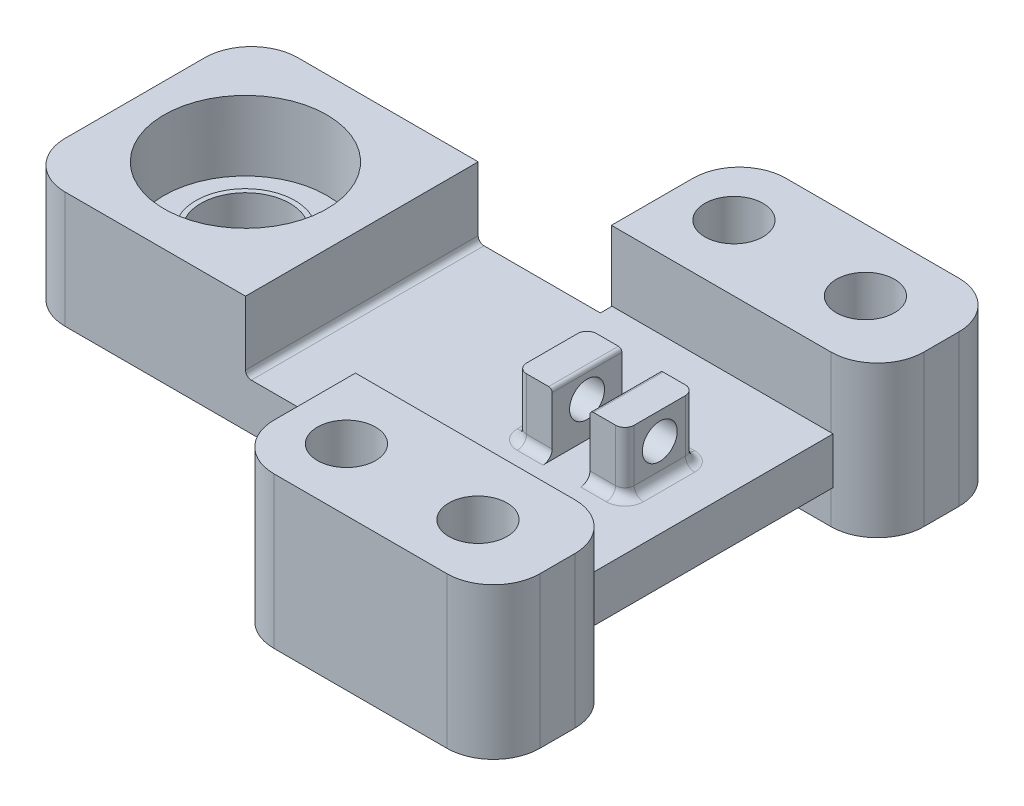
SolidWorks part; units mm, degrees
ref_plane "Front Plane" through (0, 0, 0) normal (0, 0, 1) x (1, 0, 0)
ref_plane "Top Plane" through (0, 0, 0) normal (0, 1, 0) x (1, 0, 0)
ref_plane "Right Plane" through (0, 0, 0) normal (1, 0, 0) x (0, 0, -1)
sketch "Sketch2" plane through (0, 0, 0) normal (0, 1, 0) x (1, 0, 0)
  line L1 (-14.4231, 13.5577) -> (34.5769, 13.5577)
  line L2 (-14.4231, 13.5577) -> (-14.4231, -6.4423)
  line L3 (-14.4231, -6.4423) -> (34.5769, -6.4423)
  line L4 (34.5769, 13.5577) -> (34.5769, -6.4423)
  dimension "D1" = 49
  dimension "D2" = 20
extrude "Boss-Extrude1" add sketch "Sketch2" along normal blind 10
sketch "Sketch3" plane through (0, 0, 0) normal (0, -1, 0) x (1, 0, 0)
  line L0 (34.5769, 6.4423) -> (34.5769, -13.5577) construction
  line L1 (27.5769, -5.0677) -> (-2.4231, -5.0677)
  line L2 (27.5769, -5.0677) -> (27.5769, -2.0477)
  line L3 (27.5769, -2.0477) -> (-2.4231, -2.0477)
  line L4 (-2.4231, -5.0677) -> (-2.4231, -2.0477)
  line L5 (-14.4231, -3.5577) -> (34.5769, -3.5577) construction
  line L6 (-14.4231, -13.5577) -> (-14.4231, 6.4423) construction
  dimension "D1" = 30
  dimension "D2" = 7
  dimension "D3" = 3.02
  dimension "D4" = 1.51
extrude "Cut-Extrude1" cut sketch "Sketch3" against normal blind 2
sketch "Sketch4" plane through (0, 0, 0) normal (0, -1, 0) x (1, 0, 0)
  line L0 (-2.4231, -2.0477) -> (-2.4231, -5.0677) construction
  line L1 (-2.4231, -6.5477) -> (-7.4231, -6.5477)
  line L2 (-2.4231, -6.5477) -> (-2.4231, -0.5477)
  line L3 (-2.4231, -0.5477) -> (-7.4231, -0.5477)
  line L4 (-7.4231, -6.5477) -> (-7.4231, -0.5477)
  line L6 (27.5769, -2.0477) -> (-2.4231, -2.0477) construction
  dimension "D1" = 6
  dimension "D2" = 5
  dimension "D3" = 1.5
extrude "Cut-Extrude2" cut sketch "Sketch4" against normal blind 5
sketch "Sketch5" plane through (0, 5, 0) normal (0, -1, 0) x (1, 0, 0)
  line L0 (-7.4231, -3.5477) -> (-2.4231, -3.5577) construction
  line L1 (-7.4231, -0.5477) -> (-7.4231, -6.5477) construction
  line L2 (-2.4231, -2.0477) -> (-2.4231, -5.0677) construction
  circle A0 centre (-4.9231, -3.5527) radius 7
  dimension "D1" = 14
extrude "Cut-Extrude3" cut sketch "Sketch5" against normal through all
sketch "Sketch12" plane through (0, 0, 0) normal (0, -1, 0) x (1, 0, 0)
  line L1 (-7.4231, -0.5477) -> (-2.4231, -0.5477)
  line L2 (-7.4231, -0.5477) -> (-7.4231, -6.5477)
  line L3 (-7.4231, -6.5477) -> (-2.4231, -6.5477)
  line L4 (-2.4231, -0.5477) -> (-2.4231, -6.5477)
extrude "Boss-Extrude4" add sketch "Sketch12" against normal blind 0.8
sketch "Sketch14" plane through (0, 0, 6.4423) normal (0, 0, 1) x (1, 0, 0)
  line L0 (-14.4231, 10) -> (34.5769, 10) construction
  line L1 (5.0769, 10) -> (34.5769, 10)
  line L2 (5.0769, 10) -> (5.0769, 4)
  line L3 (5.0769, 4) -> (34.5769, 4)
  line L4 (34.5769, 10) -> (34.5769, 4)
  line L5 (34.5769, 10) -> (34.5769, 0) construction
  line L6 (27.5769, 2) -> (-2.4231, 2) construction
  line L7 (2.0769, 5) -> (2.0769, 10) construction
  dimension "D1" = 2
  dimension "D2" = 3
extrude "Cut-Extrude6" cut sketch "Sketch14" against normal through all
sketch "Sketch20" plane through (0, 0.8, 0) normal (0, 1, 0) x (1, 0, 0)
  line L0 (-2.4231, 0.5477) -> (-7.4231, 0.5477) construction
  line L1 (-7.4231, 6.5477) -> (-2.4231, 6.5477)
  line L2 (-7.4231, 6.5477) -> (-7.4231, 0.5477)
  line L3 (-7.4231, 0.5477) -> (-2.4231, 0.5477)
  line L4 (-2.4231, 6.5477) -> (-2.4231, 0.5477)
  line L5 (-2.4231, 0.5477) -> (-7.4231, 0.5477) construction
extrude "Boss-Extrude6" add sketch "Sketch20" along normal up to surface (4.2 mm away) up to face at (-4.9231, 5, -10.5527)
sketch "Sketch21" plane through (0, 5, 0) normal (0, 1, 0) x (1, 0, 0)
  circle A0 centre (-4.9231, 3.5527) radius 4.6
  dimension "D1" = 9.2
extrude "Cut-Extrude8" cut sketch "Sketch21" against normal blind 0.5
sketch "Sketch22" plane through (0, 4.5, 0) normal (0, 1, 0) x (1, 0, 0)
  circle A0 centre (-4.9231, 3.5527) radius 3.825
  dimension "D1" = 7.65
extrude "Cut-Extrude9" cut sketch "Sketch22" against normal blind 4
sketch "Sketch24" plane through (0, 5, 0) normal (0, 1, 0) x (1, 0, 0)
  circle A0 centre (-4.9231, 3.5527) radius 4.25
  circle A1 centre (-4.9231, 3.5527) radius 4.6
  dimension "D1" = 9.2
  dimension "D2" = 8.5
extrude "Cut-Extrude11" cut sketch "Sketch24" against normal blind 1
sketch "Sketch26" plane through (0, 4.5, 0) normal (0, 1, 0) x (1, 0, 0)
  circle A0 centre (-4.9231, 3.5527) radius 3.825
  circle A1 centre (-4.9231, 3.5527) radius 4.25
extrude "Boss-Extrude9" add sketch "Sketch26" along normal blind 0.5
sketch "Sketch27" plane through (0, 5, 0) normal (0, 1, 0) x (1, 0, 0)
  circle A0 centre (-4.9231, 3.5527) radius 4.6
  circle A1 centre (-4.9231, 3.5527) radius 7
extrude "Cut-Extrude12" cut sketch "Sketch27" against normal blind 1
sketch "Sketch39" plane through (0, 4, 0) normal (0, 1, 0) x (1, 0, 0)
  line L0 (5.0769, 3.5577) -> (29.0295, 3.5577) construction
  line L1 (5.0769, 13.5577) -> (5.0769, -6.4423) construction
  line L4 (6.3269, -0.6923) -> (6.3269, 8.9673) construction
  line L5 (5.0769, 13.5577) -> (5.0769, -6.4423) construction
  circle A0 centre (6.3269, -0.6923) radius 0.6
  circle A1 centre (7.5769, 7.8077) radius 0.6
  circle A2 centre (9.9936, 7.8077) radius 0.6
  circle A3 centre (8.7436, -0.6923) radius 0.6
  circle A4 centre (12.4103, 7.8077) radius 0.6
  circle A5 centre (11.1603, -0.6923) radius 0.6
  circle A6 centre (14.8269, 7.8077) radius 0.6
  circle A7 centre (13.5769, -0.6923) radius 0.6
  circle A8 centre (17.2436, 7.8077) radius 0.6
  circle A9 centre (15.9936, -0.6923) radius 0.6
  circle A10 centre (19.6603, 7.8077) radius 0.6
  circle A11 centre (18.4103, -0.6923) radius 0.6
  circle A12 centre (22.0769, 7.8077) radius 0.6
  circle A13 centre (20.8269, -0.6923) radius 0.6
  circle A22 centre (24.4936, 7.8077) radius 0.6 [skipped]
  circle A23 centre (23.2436, -0.6923) radius 0.6 [skipped]
  dimension "D1" = 1.2
  dimension "D2" = 1.2
  dimension "D7" = 1.25
  dimension "D3" = 8.5
  dimension "D4" = 1.25
  dimension "D5" = 4.25
  dimension "D6" = 8
fillet "Fillet1" radius 0.5 1 edges at (5.0769, 4, -3.5577)
sketch "Sketch56" plane through (0, 0, 0) normal (0, -1, 0) x (1, 0, 0)
  line L0 (27.5769, -2.0477) -> (-2.4231, -2.0477) construction
  line L1 (-2.4231, -5.0677) -> (-2.4231, -2.0477) construction
  circle A0 centre (28.9269, -3.5577) radius 2
  dimension "D1" = 4
  dimension "D2" = 1.51
  dimension "D3" = 31.35
extrude "Cut-Extrude13" cut sketch "Sketch56" against normal up to surface (2 mm away) up to face at (13.1618, 2, -3.5578)
sketch "Sketch57" plane through (0, 4, 0) normal (0, 1, 0) x (1, 0, 0)
  line L0 (26.0569, 11.0577) -> (26.0569, -3.9423) construction
  line L1 (24.4319, 0.5577) -> (21.4319, 0.5577)
  line L2 (30.6819, 0.5577) -> (27.6819, 0.5577)
  line L3 (30.6819, 0.5577) -> (30.6819, 6.5577)
  line L4 (30.6819, 6.5577) -> (27.6819, 6.5577)
  line L5 (27.6819, 0.5577) -> (27.6819, 6.5577)
  line L6 (30.6819, 0.5577) -> (27.6819, 6.5577) construction
  line L7 (30.6819, 6.5577) -> (27.6819, 0.5577) construction
  line L8 (24.4319, 0.5577) -> (24.4319, 6.5577)
  line L9 (24.4319, 6.5577) -> (21.4319, 6.5577)
  line L10 (21.4319, 0.5577) -> (21.4319, 6.5577)
  line L11 (24.4319, 0.5577) -> (21.4319, 6.5577) construction
  line L12 (24.4319, 6.5577) -> (21.4319, 0.5577) construction
  line L13 (5.5769, 13.5577) -> (5.5769, -6.4423) construction
  line L14 (5.5769, 13.5577) -> (34.5769, 13.5577) construction
  circle A1 centre (26.0569, 3.5577) radius 6
  circle A2 centre (26.0569, 3.5577) radius 5.8
  point P6 (26.0569, 3.5577)
  point P7 (29.1819, 3.5577)
  point P19 (22.9319, 3.5577)
  dimension "D1" = 11.6
  dimension "D2" = 0.2
  dimension "D3" = 15
  dimension "D4" = 3
  dimension "D11" = 20.48
  dimension "D5" = 6
  dimension "D6" = 3.125
  dimension "D7" = 3.125
  dimension "D8" = 6
  dimension "D9" = 3
  dimension "D10" = 20.48
  dimension "D12" = 10
extrude "Boss-Extrude19" add sketch "Sketch57" along normal blind 5.3 contours L5 L2 L3 L4 | L10 L1 L8 L9 region at (22.9319, 4, -3.5577) region at (29.1819, 4, -3.5577)
sketch "Sketch58" plane through (30.6819, 0, 0) normal (1, 0, 0) x (0, 0, -1)
  line L2 (0.5577, 4) -> (6.5577, 4) construction
  line L3 (0.5577, 9.3) -> (0.5577, 4) construction
  circle A0 centre (3.5577, 7) radius 1.5
  dimension "D1" = 3
  dimension "D2" = 3
  dimension "D3" = 3
extrude "Cut-Extrude14" cut sketch "Sketch58" against normal up to surface (9.25 mm away) up to face at (21.4319, 6.65, -3.5577)
fillet "Fillet2" radius 0.3 2 edges at (24.4319, 9.3, -3.5577) (27.6819, 9.3, -3.5577)
fillet "Fillet3" radius 0.8 10 edges at (21.4319, 6.65, -0.5577) (21.4319, 6.65, -6.5577) (21.4319, 4, -3.5577) (22.9319, 4, -6.5577) (30.6819, 6.65, -6.5577) (29.1819, 4, -6.5577) (30.6819, 6.65, -0.5577) (30.6819, 4, -3.5577) (29.1819, 4, -0.5577) (22.9319, 4, -0.5577)
ref_plane "Plane1" through (0, 0, -3.5577) normal (0, 0, -1) x (-1, 0, 0)
sketch "Sketch60" plane through (0, 0, -13.5577) normal (0, 0, -1) x (-1, 0, 0)
  line L1 (-34.5769, 4) -> (-15.5769, 4)
  line L2 (-34.5769, 4) -> (-34.5769, 0)
  line L3 (-34.5769, 0) -> (-15.5769, 0)
  line L4 (-15.5769, 4) -> (-15.5769, 0)
  line L5 (-34.5769, 0) -> (14.4231, 0) construction
  dimension "D1" = 19
extrude "Boss-Extrude21" add sketch "Sketch60" along normal blind 1
sketch "Sketch59" plane through (0, 0, -14.5577) normal (0, 0, -1) x (-1, 0, 0)
  line L0 (-15.5769, 0) -> (14.4231, 0) construction
  line L1 (-38.3869, -3) -> (-15.5269, -3)
  line L2 (-38.3869, -3) -> (-38.3869, 10)
  line L3 (-38.3869, 10) -> (-15.5269, 10)
  line L4 (-15.5269, -3) -> (-15.5269, 10)
  line L5 (-34.5769, 4) -> (-34.5769, 0) construction
  dimension "D1" = 22.86
  dimension "D2" = 13
  dimension "D3" = 3
  dimension "D4" = 3.81
extrude "Boss-Extrude20" add sketch "Sketch59" along normal blind 11
ref_axis "Axis1" through (28.9269, 2, -3.5577) along (0, -1, 0)
mirror "Mirror4" about plane through (0, 0, -3.5577) normal (0, 0, -1) of "Boss-Extrude20", "Boss-Extrude21"
sketch "Sketch61" plane through (0, 10, 0) normal (0, 1, 0) x (1, 0, 0)
  line L0 (24.4319, 7.3577) -> (24.4319, 20.2077) construction
  line L1 (-14.4231, 3.5577) -> (34.5769, 3.5577) construction
  line L2 (-14.4231, 13.5577) -> (-14.4231, -6.4423) construction
  line L3 (34.5769, 14.5577) -> (34.5769, -7.4423) construction
  line L4 (24.4319, 20.2077) -> (20.4069, 20.2077) construction
  line L5 (27.6819, 7.3577) -> (27.6819, 20.2077) construction
  line L6 (27.6819, 20.2077) -> (31.7069, 20.2077) construction
  line L7 (27.6819, -13.0923) -> (31.7069, -13.0923) construction
  line L8 (27.6819, -0.2423) -> (27.6819, -13.0923) construction
  line L9 (24.4319, -13.0923) -> (20.4069, -13.0923) construction
  line L10 (24.4319, -0.2423) -> (24.4319, -13.0923) construction
  circle A0 centre (20.4069, 20.2077) radius 2.5
  circle A1 centre (31.7069, 20.2077) radius 2.5
  circle A2 centre (31.7069, -13.0923) radius 2.5
  circle A3 centre (20.4069, -13.0923) radius 2.5
  dimension "D3" = 5
  dimension "D2" = 11.3
  dimension "D4" = 16.65
extrude "Cut-Extrude15" cut sketch "Sketch61" against normal up to next
fillet "Fillet4" radius 4 8 edges at (38.3869, 3.5, -25.5577) (38.3869, 3.5, 7.4423) (38.3869, 3.5, 18.4423) (15.5269, 3.5, 18.4423) (15.5269, 3.5, -25.5577) (-14.4231, 5, -13.5577) (-14.4231, 5, 6.4423) (38.3869, 3.5, -14.5577)
